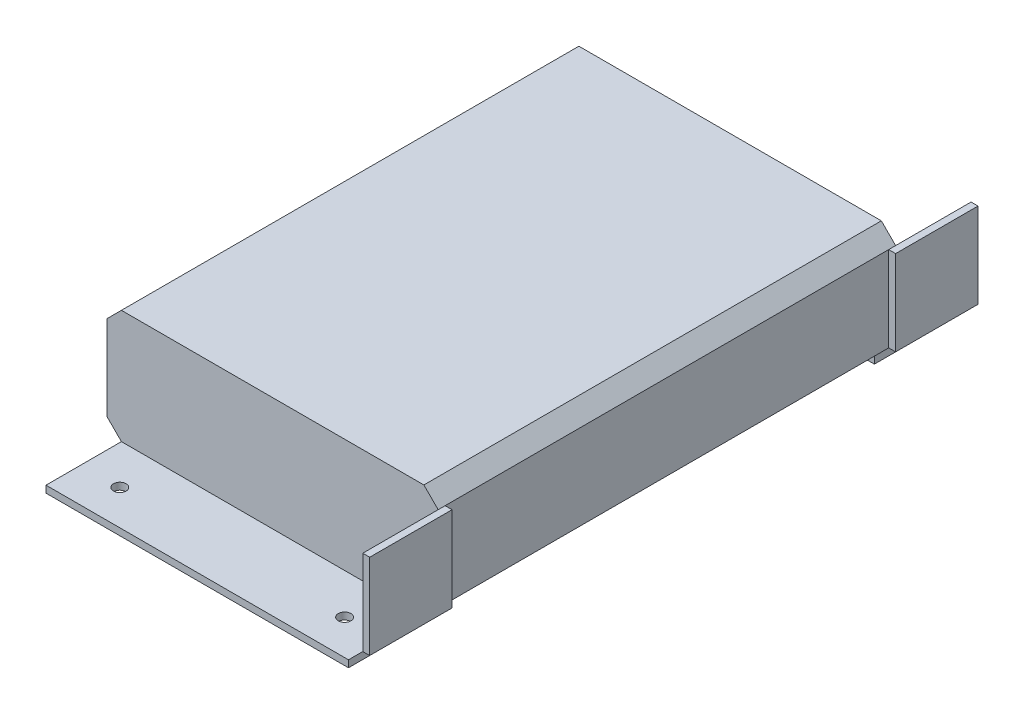
SolidWorks part; units mm, degrees
ref_plane "Front Plane" through (0, 0, 0) normal (0, 0, 1) x (1, 0, 0)
ref_plane "Top Plane" through (0, 0, 0) normal (0, 1, 0) x (1, 0, 0)
ref_plane "Right Plane" through (0, 0, 0) normal (1, 0, 0) x (0, 0, -1)
sketch "Sketch1" plane through (0, 0, 0) normal (0, 0, 1) x (1, 0, 0)
  line L1 (-41.7, -14.325) -> (41.7, -14.325)
  line L2 (-41.7, -14.325) -> (-41.7, 14.325)
  line L3 (-41.7, 14.325) -> (41.7, 14.325)
  line L4 (41.7, -14.325) -> (41.7, 14.325)
  line L5 (-41.7, -14.325) -> (41.7, 14.325) construction
  line L6 (-41.7, 14.325) -> (41.7, -14.325) construction
  point P0 (0, 0)
  dimension "D1" = 83.4
  dimension "D2" = 28.65
extrude "Boss-Extrude1" add sketch "Sketch1" along normal blind 115.25
chamfer "Chamfer1" distance 3.6 angle 45 4 edges at (-41.7, -14.325, 57.625) (41.7, -14.325, 57.625) (41.7, 14.325, 57.625) (-41.7, 14.325, 57.625)
sketch "Sketch2" plane through (0, 0, 115.25) normal (0, 0, 1) x (1, 0, 0)
  line L1 (41.7, 10.725) -> (43.45, 10.725)
  line L2 (41.7, 10.725) -> (41.7, -10.725)
  line L3 (41.7, -10.725) -> (43.45, -10.725)
  line L4 (43.45, 10.725) -> (43.45, -10.725)
  line L5 (38.1, -14.325) -> (-38.1, -14.325)
  line L6 (38.1, -14.325) -> (38.1, -16.075)
  line L7 (38.1, -16.075) -> (-38.1, -16.075)
  line L8 (-38.1, -14.325) -> (-38.1, -16.075)
  dimension "D1" = 1.75
  dimension "D2" = 1.75
extrude "Boss-Extrude2" add sketch "Sketch2" along normal blind 19 and the other way blind 1.75
extrude "Boss-Extrude4" add sketch "Sketch2<2>" against normal blind 19 and the other way blind 1.75 from offset 115.25 offset against normal yes
sketch "Sketch2<2>" plane through (0, 0, 115.25) normal (0, 0, 1) x (1, 0, 0) same geometry as "Sketch2"
sketch "Sketch3" plane through (0, -14.325, 0) normal (0, 1, 0) x (1, 0, 0)
  line L0 (0, 0) -> (0, -115.25) construction
  line L1 (-38.1, -115.25) -> (38.1, -115.25) construction
  line L2 (0, -57.625) -> (-90.3546, -57.625) construction
  circle A0 centre (-28.321, 10.193) radius 1.6
  circle A1 centre (28.321, 10.193) radius 1.6
  circle A2 centre (28.321, -125.443) radius 1.6
  circle A3 centre (-28.321, -125.443) radius 1.6
  dimension "D1" = 3.2
  dimension "D2" = 56.642
  dimension "D3" = 135.636
extrude "Cut-Extrude1" cut sketch "Sketch3" against normal through all
